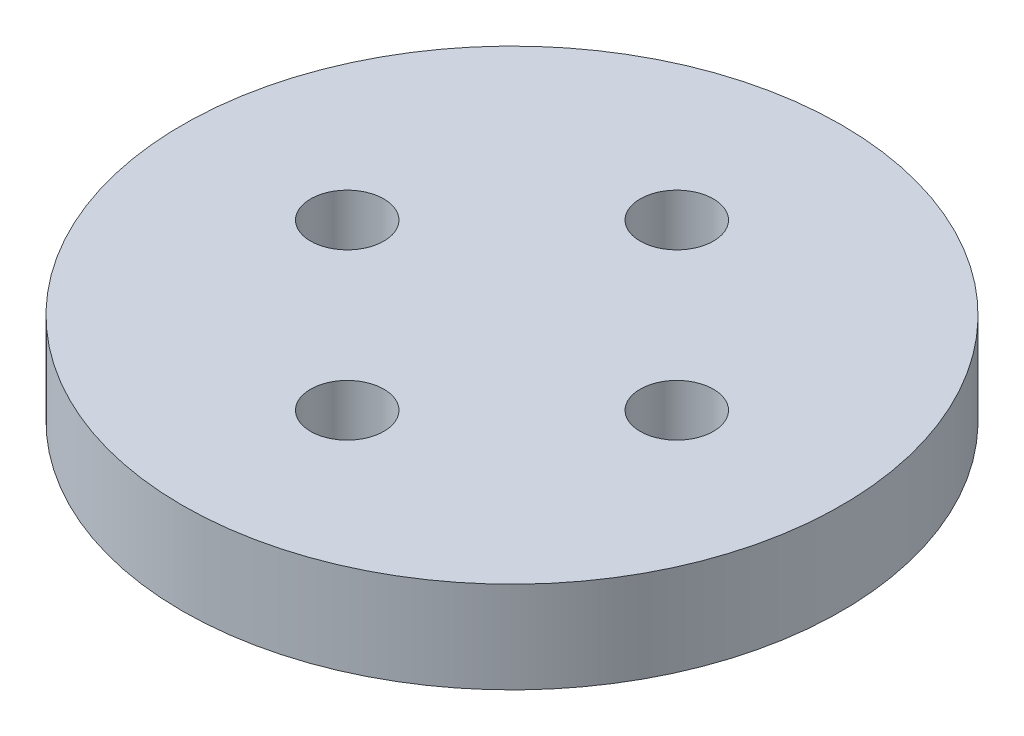
SolidWorks part; units mm, degrees
ref_plane "前视基准面" through (0, 0, 0) normal (0, 0, 1) x (1, 0, 0)
ref_plane "上视基准面" through (0, 0, 0) normal (0, 1, 0) x (1, 0, 0)
ref_plane "右视基准面" through (0, 0, 0) normal (1, 0, 0) x (0, 0, -1)
sketch "草图1" plane through (0, 0, 0) normal (0, 1, 0) x (1, 0, 0)
  circle A0 centre (0, 0) radius 18
  circle A1 centre (0, 0) radius 9 construction
  circle A2 centre (0, 9) radius 2
  circle A3 centre (9, 0) radius 2
  circle A4 centre (-9, 0) radius 2
  circle A5 centre (0, -9) radius 2
  dimension "D1" = 36
  dimension "D2" = 18
  dimension "D3" = 4
  dimension "D4" = 4
  dimension "D5" = 4
  dimension "D6" = 4
extrude "凸台-拉伸1" add sketch "草图1" along normal blind 5
